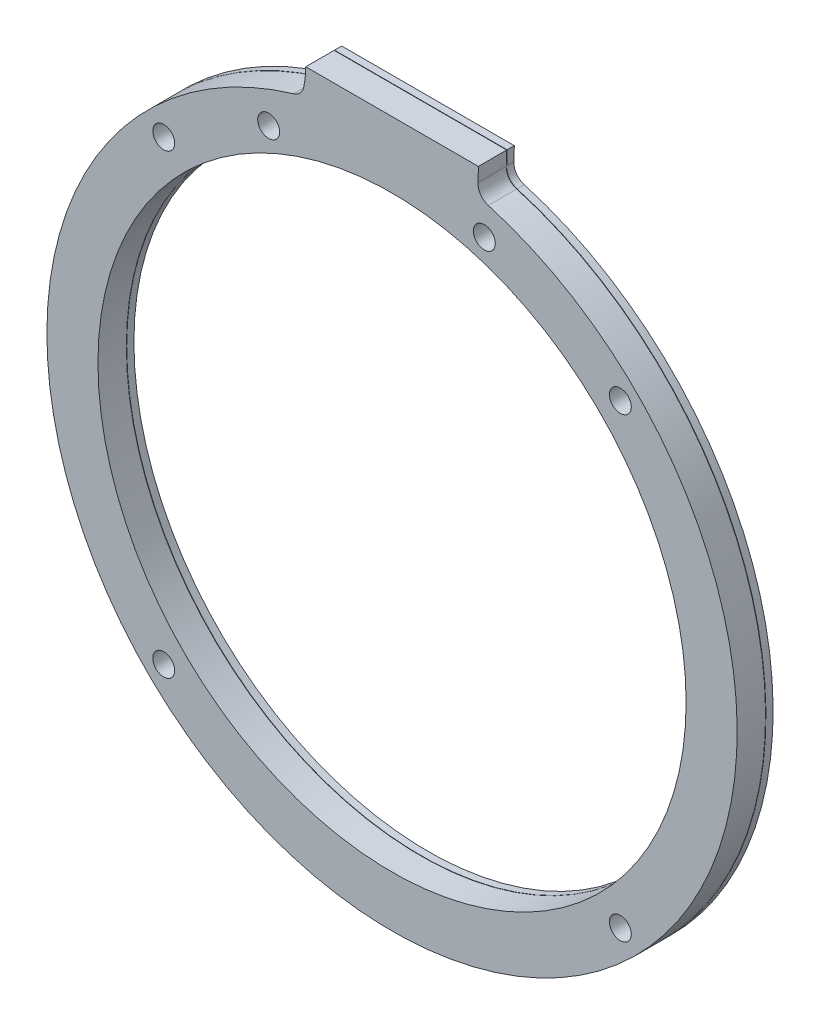
SolidWorks part; units mm, degrees
material "Thornel Mat VMA"
ref_plane "前视基准面" through (0, 0, 0) normal (0, 0, 1) x (1, 0, 0)
ref_plane "上视基准面" through (0, 0, 0) normal (0, 1, 0) x (1, 0, 0)
ref_plane "右视基准面" through (0, 0, 0) normal (1, 0, 0) x (0, 0, -1)
sketch "草图1" plane through (0, 0, 0) normal (0, 0, 1) x (1, 0, 0)
  line L0 (0, 0) -> (0, 50.1) construction
  line L1 (0, 50.1) -> (0, 73.1) construction
  line L2 (-35.5, 73.1) -> (35.5, 73.1) construction
  line L3 (-12, 50.1) -> (12, 50.1)
  line L4 (0, 0) -> (12.8351, 41.9818) construction
  line L5 (0, 0) -> (-17.1531, 40.4102) construction
  circle A0 centre (0, 0) radius 19.04 construction
  circle A1 centre (0, 0) radius 40.9
  circle A2 centre (0, 0) radius 21 construction
  circle A3 centre (-14.8492, 14.8492) radius 1.525 construction
  circle A4 centre (14.8492, 14.8492) radius 1.525 construction
  circle A5 centre (14.8492, -14.8492) radius 1.525 construction
  circle A6 centre (-14.8492, -14.8492) radius 1.525 construction
  circle A7 centre (0, 0) radius 46.4 construction
  circle A8 centre (-35.5, 73.1) radius 30 construction
  circle A9 centre (35.5, 73.1) radius 30 construction
  arc A10 (0, 50.1) -> (-6.8598, 33.3008) centre (-24, 50.1) cw construction
  circle A11 centre (0, 0) radius 34 construction
  circle A12 centre (-1.2412, 42.4819) radius 8.5 construction
  circle A13 centre (0, 59.4365) radius 8.5 construction
  arc A15 (-13.6688, 46.0127) -> (13.3851, 46.096) centre (0, 0) ccw
  arc A18 (-12, 50.1) -> (-12.286, 47.4958) centre (-24, 50.1) cw
  arc A19 (12, 50.1) -> (11.9459, 48.1263) centre (-24, 50.1) cw
  arc A20 (-12.286, 47.4958) -> (-13.6688, 46.0127) centre (-14.2383, 47.9298) cw
  arc A21 (11.9459, 48.1263) -> (13.3851, 46.096) centre (13.9428, 48.0166) ccw
  circle A22 centre (-17.1531, 40.4102) radius 1.525
  circle A23 centre (12.8351, 41.9818) radius 1.525
  point P17 (0, 0)
  dimension "D2" = 38.08
  dimension "D3" = 81.8
  dimension "D4" = 42
  dimension "D6" = 3.05
  dimension "D8" = 60
  dimension "D10" = 24
  dimension "D11" = 68
  dimension "D12" = 17
  dimension "D13" = 92.8
  dimension "D14" = 96
  dimension "D16" = 2
  dimension "D17" = 3.05
  dimension "D1" = 50.1
  dimension "D7" = 71
  dimension "D9" = 23
  dimension "D15" = 24
  dimension "D18" = 43.9
  dimension "D19" = 17
  dimension "D20" = 40
  dimension "D5" = 4
extrude "凸台-拉伸1" add sketch "草图1" along normal blind 5
sketch "草图2" plane through (0, 0, 5) normal (0, 0, 1) x (1, 0, 0)
  circle A0 centre (0, 0) radius 44.9 construction
  circle A1 centre (-31.7491, 31.7491) radius 1.525
  circle A2 centre (31.7491, 31.7491) radius 1.525
  circle A3 centre (31.7491, -31.7491) radius 1.525
  circle A4 centre (-31.7491, -31.7491) radius 1.525
  point P15 (0, 0)
  dimension "D2" = 3.05
  dimension "D3" = 89.8
  dimension "D1" = 4
extrude "切除-拉伸1" cut sketch "草图2" against normal blind 10
sketch "草图3" plane through (0, 0, 0) normal (0, 1, 0) x (1, 0, 0)
  line L0 (48, 0) -> (-48, 0) construction
  line L1 (-52.486, -1) -> (55.3452, -1)
  line L2 (-52.486, -1) -> (-52.486, -1.05)
  line L3 (-52.486, -1.05) -> (55.3452, -1.05)
  line L4 (55.3452, -1) -> (55.3452, -1.05)
  dimension "D1" = 0.05
  dimension "D2" = 1
extrude "切除-拉伸2" cut sketch "草图3" against normal through all both and the other way through all
